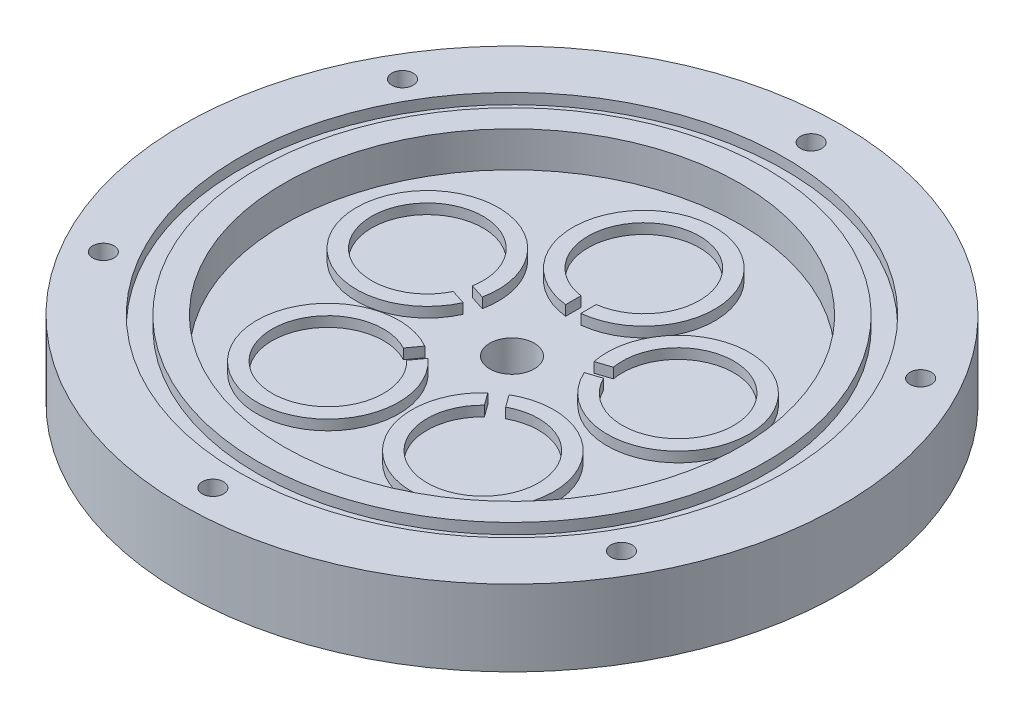
SolidWorks part; units mm, degrees
ref_plane "Alzado" through (0, 0, 0) normal (0, 0, 1) x (1, 0, 0)
ref_plane "Planta" through (0, 0, 0) normal (0, 1, 0) x (1, 0, 0)
ref_plane "Vista lateral" through (0, 0, 0) normal (1, 0, 0) x (0, 0, -1)
sketch "Croquis2" plane through (0, 0, 0) normal (0, 1, 0) x (1, 0, 0)
  circle A0 centre (0, 0) radius 65
  circle A1 centre (0, 0) radius 15 construction
  circle A2 centre (0, 0) radius 45
  circle A3 centre (0, 0) radius 26 construction
  circle A4 centre (0, 26) radius 11
  circle A5 centre (0, 0) radius 59 construction
  circle A6 centre (0, 59) radius 2.5 construction
  circle A7 centre (0, 0) radius 51.945 construction
  circle A8 centre (0, 51.945) radius 1.31 construction
  dimension "D1" = 22
  dimension "D2" = 30
  dimension "D3" = 130
  dimension "D4" = 90
  dimension "D5" = 5
  dimension "D7" = 2.62
  dimension "D8" = 103.89
  dimension "D6" = 6
extrude "Saliente-Extruir1" add sketch "Croquis2" against normal blind 15 contours A0
extrude "Cortar-Extruir1" cut sketch "Croquis2<3>" against normal blind 7 contours A2
sketch "Croquis2<3>" plane through (0, 0, 0) normal (0, 1, 0) x (1, 0, 0) same geometry as "Croquis2"
hole_wizard "Taladro roscado G1/81" positions "Croquis4" profile "Croquis5" tap size "G1/8" standard "GB" end condition through all
sketch "Croquis4" plane through (0, -15, 0) normal (0, -1, 0) x (-1, 0, 0)
  point P0 (0, 0)
sketch "Croquis5" plane through (0, -15, 0) normal (1, 0, 0) x (0, 0, -1)
  line L0 (0, 0) -> (0, 15)
  line L1 (0, 15) -> (4.4, 15)
  line L2 (4.4, 15) -> (4.4, 0)
  line L5 (4.4, 0) -> (0, 0)
  line L11 (0, -6.35) -> (0, 107.95) construction
  dimension "Diámetro de perforador para roscar hasta el siguiente" = 8.8
  dimension "Profundidad de perforador para roscar hasta el siguiente" = 15
cosmetic thread "Rosca de taladro1"
sketch "Croquis3" plane through (0, -7, 0) normal (0, 1, 0) x (1, 0, 0)
  circle A0 centre (0, 26) radius 14
  circle A1 centre (0, 26) radius 11 construction
  circle A2 centre (0, 26) radius 11
  dimension "D1" = 3
extrude "Saliente-Extruir3" add sketch "Croquis3" along normal blind 2 contours A0 | A2
sketch "Croquis6" plane through (0, -7, 0) normal (0, 1, 0) x (1, 0, 0)
  line L0 (0, 26) -> (0, 4.4) construction
  line L1 (1.5, 26) -> (1.5, 4.4)
  line L2 (-1.5, 26) -> (-1.5, 4.4)
  circle A0 centre (0, 0) radius 4.4 construction
  arc A1 (1.5, 26) -> (-1.5, 26) centre (0, 26) ccw
  arc A2 (-1.5, 4.4) -> (1.5, 4.4) centre (0, 4.4) ccw
  point P6 (0, 15.2)
  dimension "D1" = 3
extrude "Cortar-Extruir3" cut sketch "Croquis6" along normal through all
pattern_circular "MatrizC1" count 5 over 360 about axis through (0, -15, 0) along (0, 1, 0) of "Saliente-Extruir3", "Cortar-Extruir3" reverse direction yes
sketch "Croquis7" plane through (0, 0, 0) normal (1, 0, 0) x (0, 0, -1)
  line L1 (53.795, 2.1) -> (50.095, 2.1)
  line L2 (53.795, 2.1) -> (53.795, -2.1)
  line L3 (53.795, -2.1) -> (50.095, -2.1)
  line L4 (50.095, 2.1) -> (50.095, -2.1)
  line L5 (53.795, 2.1) -> (50.095, -2.1) construction
  line L6 (53.795, -2.1) -> (50.095, 2.1) construction
  line L9 (0, 0) -> (0, -28.3585) construction
  point P0 (51.945, 0)
  dimension "D1" = 4.2
  dimension "D2" = 3.7
revolve "Cortar-Revolución1" cut sketch "Croquis7" angle 360 about L9
hole_wizard "Taladro roscado M51" positions "Croquis8" profile "Croquis9" tap size "M5" standard "DIN" end condition through all
sketch "Croquis8" plane through (0, 0, 0) normal (0, 1, 0) x (1, 0, 0)
  point P0 (0, 59)
sketch "Croquis9" plane through (0, 0, -59) normal (1, 0, 0) x (0, 0, 1)
  line L0 (0, 0) -> (0, 15)
  line L1 (0, 15) -> (2.1, 15)
  line L2 (2.1, 15) -> (2.1, 0)
  line L5 (2.1, 0) -> (0, 0)
  line L11 (0, -6.35) -> (0, 107.95) construction
  dimension "Diámetro de perforador para roscar hasta el siguiente" = 4.2
  dimension "Profundidad de perforador para roscar hasta el siguiente" = 15
cosmetic thread "Rosca de taladro2"
pattern_circular "MatrizC2" count 6 over 360 about axis through (0, -15, 0) along (0, 1, 0) of "Taladro roscado M51" reverse direction yes
equation "\"D1@Croquis7\"=2.10*2"
equation "\"D8@Croquis2\"=(106.51+101.27)/2"
